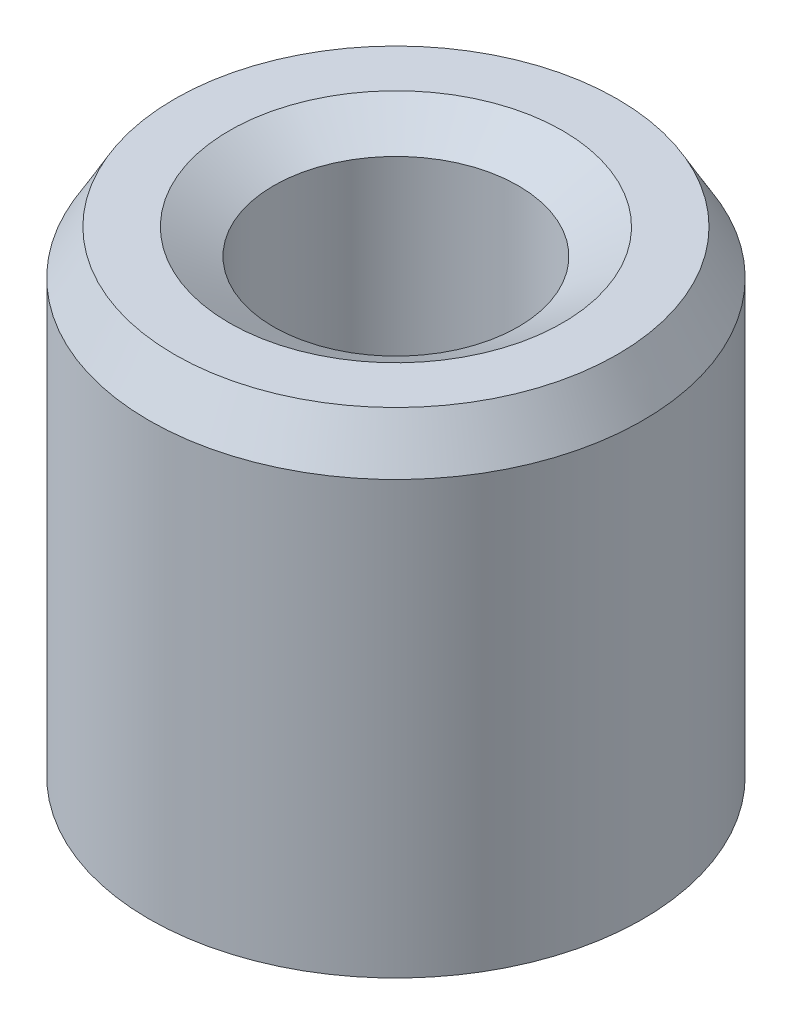
SolidWorks part; units mm, degrees
ref_plane "Front Plane" through (0, 0, 0) normal (0, 0, 1) x (1, 0, 0)
ref_plane "Top Plane" through (0, 0, 0) normal (0, 1, 0) x (1, 0, 0)
ref_plane "Right Plane" through (0, 0, 0) normal (1, 0, 0) x (0, 0, -1)
sketch "Sketch1" plane through (0, 0, 0) normal (0, 1, 0) x (1, 0, 0)
  circle A0 centre (0, 0) radius 17.5
  dimension "SLEEVE_OD" = 35
extrude "Boss-Extrude1" add sketch "Sketch1" along normal blind 35.5439
sketch "Sketch2" plane through (0, 0, 0) normal (0, 1, 0) x (1, 0, 0)
  circle A0 centre (0, 0) radius 8.6689
  dimension "BORE_D" = 17.3379
extrude "Cut-Extrude1" cut sketch "Sketch2" along normal through all
chamfer "Chamfer1" distance 3.1372 angle 30 4 edges at (0, 35.5439, 8.6689) (0, 0, 8.6689) (0, 0, 17.5) (0, 35.5439, 17.5) first distance on face at (0, 35.5439, 8.6689) first distance on face at (0, 0, 8.6689) first distance on face at (0, 35.5439, 17.5)
